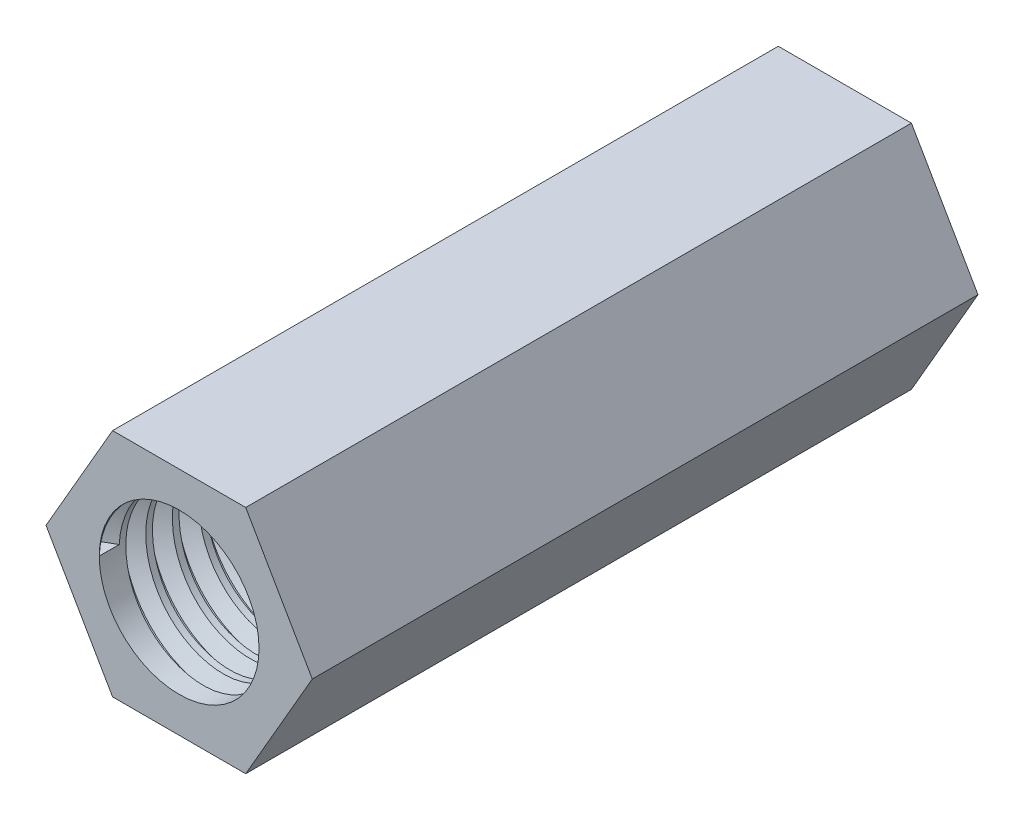
SolidWorks part; units mm, degrees
material "1.7036 (28CrS4)"
ref_plane "Plan de face" through (0, 0, 0) normal (0, 0, 1) x (1, 0, 0)
ref_plane "Plan de dessus" through (0, 0, 0) normal (0, 1, 0) x (1, 0, 0)
ref_plane "Plan de droite" through (0, 0, 0) normal (1, 0, 0) x (0, 0, -1)
sketch "Esquisse1" plane through (0, 0, 0) normal (0, 0, 1) x (1, 0, 0)
  line L0 (0, 2) -> (4, 2) construction
  line L1 (0, 0) -> (4, 0) construction
  line L2 (0, 0) -> (0, 4) construction
  line L3 (0, 4) -> (4, 4) construction
  line L4 (4, 0) -> (4, 4) construction
  line L5 (2, 4) -> (2, 0) construction
  line L7 (3, 0.2679) -> (4, 2)
  line L8 (4, 2) -> (3, 3.7321)
  line L9 (3, 3.7321) -> (1, 3.7321)
  line L10 (1, 3.7321) -> (0, 2)
  line L11 (0, 2) -> (1, 0.2679)
  line L12 (1, 0.2679) -> (3, 0.2679)
  circle A0 centre (2, 2) radius 2 construction
  dimension "D3" = 4
  dimension "D1" = 4
  dimension "D2" = 4
extrude "Boss.-Extru.1" add sketch "Esquisse1" along normal blind 10
sketch "Esquisse2" plane through (0, 0, 10) normal (0, 0, 1) x (1, 0, 0)
  line L0 (2, 3.7321) -> (2, 0.2679) construction
  line L1 (0.5, 1.134) -> (3.5, 2.866) construction
  line L6 (1, 0.2679) -> (3, 0.2679)
  line L7 (3, 0.2679) -> (4, 2)
  line L8 (4, 2) -> (3, 3.7321)
  line L9 (3, 3.7321) -> (1, 3.7321)
  line L10 (1, 3.7321) -> (0, 2)
  line L11 (0, 2) -> (1, 0.2679)
  line L12 (1, 0.2679) -> (3, 0.2679)
  line L13 (3, 0.2679) -> (4, 2)
  line L14 (4, 2) -> (3, 3.7321)
  line L15 (3, 3.7321) -> (1, 3.7321)
  line L16 (1, 3.7321) -> (0, 2)
  line L17 (0, 2) -> (1, 0.2679)
  circle A0 centre (2, 2) radius 1
  dimension "D2" = 2
  dimension "D1" = 0
hole_wizard "Dégagement M21" positions "Esquisse6" profile "Esquisse7" hole size "M2" standard "ISO"
sketch "Esquisse6" plane through (0, 0, 10) normal (0, 0, 1) x (1, 0, 0)
  point P0 (2, 2)
sketch "Esquisse7" plane through (2, 2, 10) normal (1, 0, 0) x (0, -1, 0)
  line L0 (0, 0) -> (0, 4.721)
  line L1 (0, 4.721) -> (1.2, 4)
  line L2 (1.2, 4) -> (1.2, 0)
  line L5 (1.2, 0) -> (0, 0)
  line L10 (0, 4.721) -> (-1.2, 4) construction
  line L11 (0, -6.35) -> (0, 107.95) construction
  dimension "Diamètre du perçage" = 2.4
  dimension "Profondeur du perçage" = 4
  dimension "Angle de pointe" = 118
thread "Filetage1" pitch 0.4 method cut profile "Profil de filetage1" start angle 0, offset 0, length 4, pitch 0.4, diameter 2.4
ref_plane "Plan1" through (0.8, 2, 10) normal (0, -1, 0) x (-1, 0, 0)
sketch "Profil de filetage1" plane through (0.8, 2, 10) normal (0, -1, 0) x (-1, 0, 0)
  line L0 (0, 0) -> (0, 0.4) construction
  line L1 (0, 0) -> (0.2165, 0.125)
  line L2 (0.2165, 0.125) -> (0.2165, 0.175)
  line L3 (0.2165, 0.175) -> (0, 0.3)
  line L4 (0.2165, 0.15) -> (0, 0.15) construction
  line L11 (0, 0) -> (0, 0.3)
  point P2 (0, 0)
  dimension "Pitch" = 0.4
  dimension "Profile_Angle" = 60
  dimension "Profile_Land" = 0.05
  dimension "Profile_Height" = 0.2165
hole_wizard "Dégagement M22" positions "Esquisse10" profile "Esquisse11" hole size "M2" standard "ISO"
sketch "Esquisse10" plane through (0, 0, 0) normal (0, 0, -1) x (-1, 0, 0)
  point P0 (-2, 2)
sketch "Esquisse11" plane through (2, 2, 0) normal (1, 0, 0) x (0, 1, 0)
  line L0 (0, 0) -> (0, 4.721)
  line L1 (0, 4.721) -> (1.2, 4)
  line L2 (1.2, 4) -> (1.2, 0)
  line L5 (1.2, 0) -> (0, 0)
  line L10 (0, 4.721) -> (-1.2, 4) construction
  line L11 (0, -6.35) -> (0, 107.95) construction
  dimension "Diamètre du perçage" = 2.4
  dimension "Profondeur du perçage" = 4
  dimension "Angle de pointe" = 118
thread "Filetage2" pitch 0.4 method cut profile "Profil de filetage2" start angle 0, offset 0, length 4, pitch 0.4, diameter 2.4
ref_plane "Plan2" through (3.2, 2, 0) normal (0, -1, 0) x (1, 0, 0)
sketch "Profil de filetage2" plane through (3.2, 2, 0) normal (0, -1, 0) x (1, 0, 0)
  line L0 (0, 0) -> (0, 0.4) construction
  line L1 (0, 0) -> (0.2165, 0.125)
  line L2 (0.2165, 0.125) -> (0.2165, 0.175)
  line L3 (0.2165, 0.175) -> (0, 0.3)
  line L4 (0.2165, 0.15) -> (0, 0.15) construction
  line L11 (0, 0) -> (0, 0.3)
  point P2 (0, 0)
  dimension "Pitch" = 0.4
  dimension "Profile_Angle" = 60
  dimension "Profile_Land" = 0.05
  dimension "Profile_Height" = 0.2165
equation "\"diam_cercle_circons\" = 4"
equation "\"D1@Esquisse1\"=\"diam_cercle_circons\""
equation "\"D2@Esquisse1\"=\"diam_cercle_circons\""
equation "\"Hauteur\"= 10"
equation "\"D1@Boss.-Extru.1\"=\"Hauteur\""
equation "\"D3@Esquisse1\"=\"diam_cercle_circons\""
